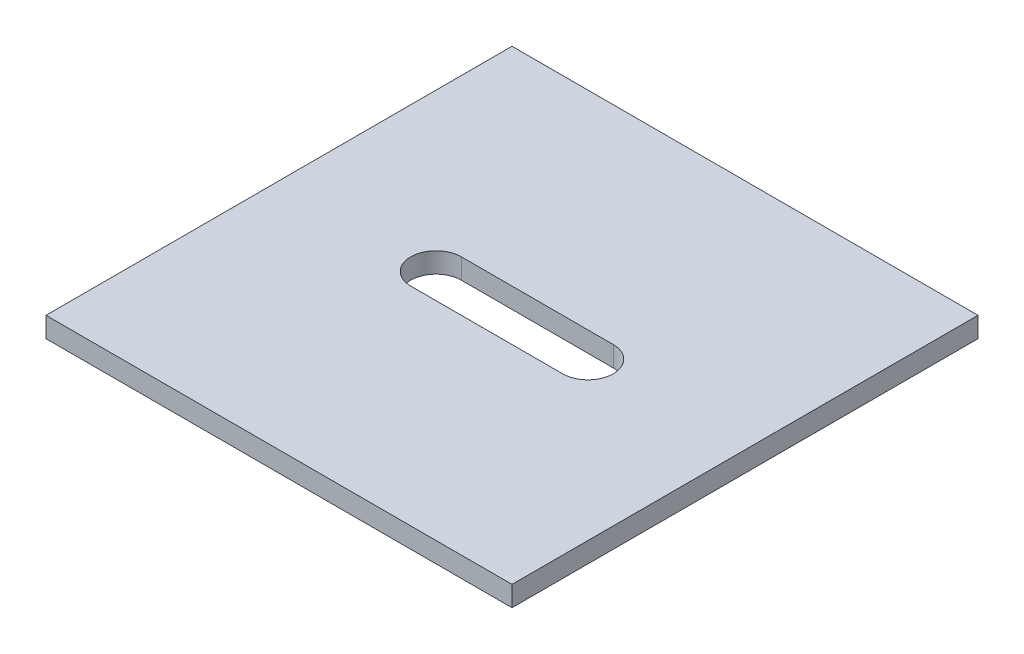
SolidWorks part; units mm, degrees
material "Pine"
ref_plane "Front Plane" through (0, 0, 0) normal (0, 0, 1) x (1, 0, 0)
ref_plane "Top Plane" through (0, 0, 0) normal (0, 1, 0) x (1, 0, 0)
ref_plane "Right Plane" through (0, 0, 0) normal (1, 0, 0) x (0, 0, -1)
sketch "Sketch2" plane through (0, 0, 0) normal (0, 1, 0) x (1, 0, 0)
  line L4 (93, 138) -> (183, 138) construction
  line L5 (0, 0) -> (276, 0)
  line L6 (0, 0) -> (0, 276)
  line L7 (0, 276) -> (276, 276)
  line L8 (276, 0) -> (276, 276)
  line L9 (93, 153) -> (183, 153)
  line L10 (93, 123) -> (183, 123)
  arc A0 (93, 153) -> (93, 123) centre (93, 138) ccw
  arc A1 (183, 123) -> (183, 153) centre (183, 138) ccw
  point P7 (138, 138)
  dimension "D3" = 138
  dimension "D5" = 15
  dimension "D1" = 276
  dimension "D2" = 276
  dimension "D4" = 93
  dimension "D6" = 90
extrude "Boss-Extrude1" add sketch "Sketch2" along normal blind 12 contours L7 L8 L5 L6
extrude "Cut-Extrude1" cut sketch "Sketch2<3>" along normal up to surface (12 mm away) contours A0 L10 A1 L9 up to face at (138, 12, -138)
sketch "Sketch2<3>" plane through (0, 0, 0) normal (0, 1, 0) x (1, 0, 0) same geometry as "Sketch2"
equation "\"LENGTH\" = 1000mm"
equation "\"PLY\"= 12mm"
equation "\"D1@Boss-Extrude1\"=\"PLY\""
